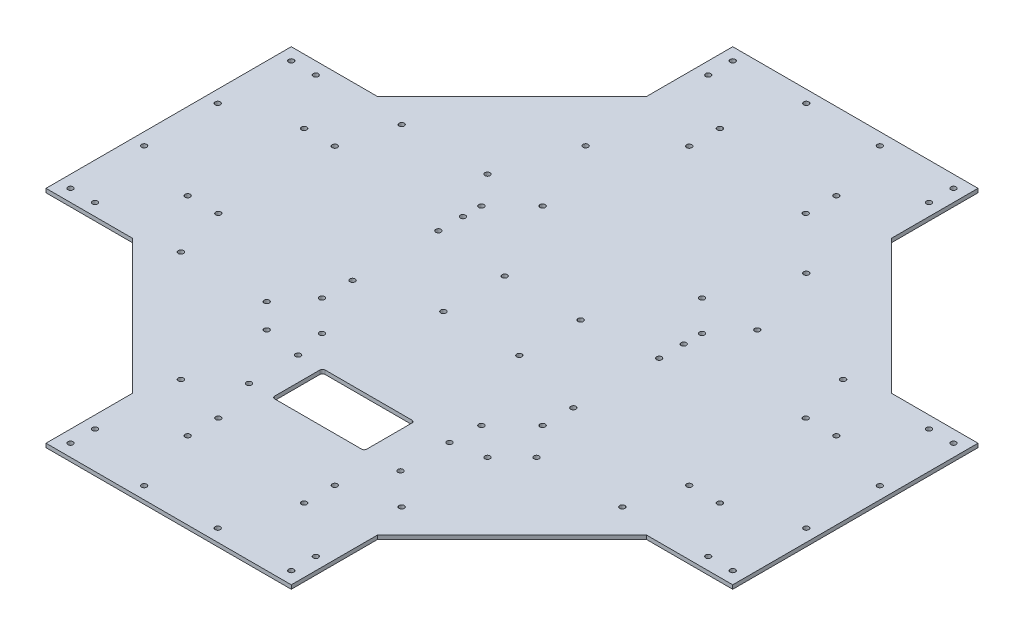
SolidWorks part; units mm, degrees
ref_plane "Front Plane" through (0, 0, 0) normal (0, 0, 1) x (1, 0, 0)
ref_plane "Top Plane" through (0, 0, 0) normal (0, 1, 0) x (1, 0, 0)
ref_plane "Right Plane" through (0, 0, 0) normal (1, 0, 0) x (0, 0, -1)
sketch "Sketch1" plane through (0, 0, 0) normal (0, 1, 0) x (1, 0, 0)
  line L0 (0, -280) -> (100, -280)
  line L1 (100, -280) -> (100, -209.6016)
  line L2 (280, -100) -> (209.6016, -100)
  line L3 (0, 0) -> (0, -280) construction
  line L4 (280, 0) -> (280, -100)
  line L5 (-280, 280) -> (280, 280) construction
  line L6 (-280, 280) -> (-280, -280) construction
  line L7 (-280, -280) -> (280, -280) construction
  line L8 (280, 280) -> (280, -280) construction
  line L9 (-280, 280) -> (280, -280) construction
  line L10 (-280, -280) -> (280, 280) construction
  line L11 (100, -209.6016) -> (209.6016, -100)
  line L12 (-280, 0) -> (-280, -100)
  line L13 (-280, -100) -> (-209.6016, -100)
  line L14 (-209.6016, -100) -> (-100, -209.6016)
  line L15 (-100, -280) -> (-100, -209.6016)
  line L16 (0, -280) -> (-100, -280)
  line L17 (0, 280) -> (-100, 280)
  line L18 (-100, 280) -> (-100, 209.6016)
  line L19 (-100, 209.6016) -> (-209.6016, 100)
  line L20 (-280, 100) -> (-209.6016, 100)
  line L21 (-280, 0) -> (-280, 100)
  line L22 (280, 0) -> (280, 100)
  line L23 (280, 100) -> (209.6016, 100)
  line L24 (209.6016, 100) -> (100, 209.6016)
  line L25 (100, 280) -> (100, 209.6016)
  line L26 (0, 280) -> (100, 280)
  line L27 (111.5258, -219.2889) -> (219.2889, -111.5258) construction
  line L28 (219.2889, -111.5258) -> (247.5732, -139.8101) construction
  line L29 (247.5732, -139.8101) -> (139.8101, -247.5732) construction
  line L30 (139.8101, -247.5732) -> (111.5258, -219.2889) construction
  line L31 (-100, -270) -> (100, -270) construction
  line L32 (-90, -280) -> (-90, 280) construction
  line L33 (-75, -75) -> (75, -75) construction
  line L34 (-75, -75) -> (-75, 75) construction
  line L35 (-75, 75) -> (75, 75) construction
  line L36 (75, -75) -> (75, 75) construction
  line L37 (-75, -75) -> (75, 75) construction
  line L38 (-75, 75) -> (75, -75) construction
  line L39 (-100, -260) -> (100, -260) construction
  line L40 (-280, 40) -> (280, 40) construction
  line L41 (0, 280) -> (0, 0) construction
  line L42 (-280, -90) -> (280, -90) construction
  line L43 (-260, -100) -> (-260, 100) construction
  line L44 (0, 0) -> (-280, 0) construction
  arc A0 (100, -280) -> (280, -100) centre (100, -100) ccw construction
  circle A1 centre (-47.5, -192) radius 2.125
  circle A2 centre (-47.5, -217) radius 2.125
  circle A3 centre (47.5, -217) radius 2.125
  circle A4 centre (47.5, -192) radius 2.125
  circle A5 centre (-192, 47.5) radius 2.125
  circle A6 centre (-217, 47.5) radius 2.125
  circle A7 centre (-192, -47.5) radius 2.125
  circle A8 centre (-217, -47.5) radius 2.125
  circle A9 centre (47.5, 192) radius 2.125
  circle A10 centre (47.5, 217) radius 2.125
  circle A11 centre (-47.5, 192) radius 2.125
  circle A12 centre (-47.5, 217) radius 2.125
  circle A13 centre (192, -47.5) radius 2.125
  circle A14 centre (217, -47.5) radius 2.125
  circle A15 centre (192, 47.5) radius 2.125
  circle A16 centre (217, 47.5) radius 2.125
  circle A17 centre (-90, -270) radius 2.125
  circle A18 centre (-30, -270) radius 2.125
  circle A19 centre (30, -270) radius 2.125
  circle A20 centre (90, -270) radius 2.125
  circle A21 centre (-270, 90) radius 2.125
  circle A22 centre (-270, 30) radius 2.125
  circle A23 centre (-270, -30) radius 2.125
  circle A24 centre (-270, -90) radius 2.125
  circle A25 centre (90, 270) radius 2.125
  circle A26 centre (30, 270) radius 2.125
  circle A27 centre (-30, 270) radius 2.125
  circle A28 centre (-90, 270) radius 2.125
  circle A29 centre (270, -90) radius 2.125
  circle A30 centre (270, -30) radius 2.125
  circle A31 centre (270, 30) radius 2.125
  circle A32 centre (270, 90) radius 2.125
  circle A33 centre (-90, -250) radius 2.125
  circle A34 centre (-90, -180) radius 2.125
  circle A35 centre (-90, -110) radius 2.125
  circle A36 centre (-90, -40) radius 2.125
  circle A37 centre (-90, 30) radius 2.125
  circle A38 centre (-90, 50) radius 2.125
  circle A39 centre (-90, 100) radius 2.125 construction
  circle A40 centre (-90, 150) radius 2.125
  circle A41 centre (-90, 200) radius 2.125 construction
  circle A42 centre (-90, 250) radius 2.125
  circle A43 centre (90, -250) radius 2.125
  circle A44 centre (90, -180) radius 2.125
  circle A45 centre (90, -110) radius 2.125
  circle A46 centre (90, -40) radius 2.125
  circle A47 centre (90, 30) radius 2.125
  circle A48 centre (90, 50) radius 2.125
  circle A49 centre (90, 100) radius 2.125 construction
  circle A50 centre (90, 150) radius 2.125
  circle A51 centre (90, 200) radius 2.125 construction
  circle A52 centre (90, 250) radius 2.125
  circle A53 centre (-250, -90) radius 2.125
  circle A54 centre (-180, -90) radius 2.125
  circle A55 centre (-110, -90) radius 2.125
  circle A56 centre (-110, 90) radius 2.125
  circle A57 centre (-180, 90) radius 2.125
  circle A58 centre (-250, 90) radius 2.125
  circle A59 centre (110, -90) radius 2.125
  circle A60 centre (180, -90) radius 2.125
  circle A61 centre (250, -90) radius 2.125
  circle A62 centre (110, 90) radius 2.125
  circle A63 centre (180, 90) radius 2.125
  circle A64 centre (250, 90) radius 2.125
  point P33 (0, 0)
  point P68 (0, 0)
  point P107 (0, 0)
  dimension "D10" = 25
  dimension "4.25" = 4.25
  dimension "D11" = 4.25
  dimension "D16" = 4.25
  dimension "D24" = 4.25
  dimension "D28" = 4.25
  dimension "D32" = 4.25
  dimension "D1" = 560
  dimension "D2" = 90
  dimension "D3" = 280
  dimension "D4" = 4
  dimension "D5" = 100
  dimension "D6" = 155
  dimension "D7" = 152.4
  dimension "D8" = 15
  dimension "D9" = 40
  dimension "D12" = 47.5
  dimension "D13" = 63
  dimension "D15" = 10
  dimension "D17" = 10
  dimension "D18" = 76.2
  dimension "D19" = 150
  dimension "D20" = 150
  dimension "D23" = 10
  dimension "D25" = 10
  dimension "D26" = 300
  dimension "D29" = 10
  dimension "D31" = 20
  dimension "D33" = 10
  dimension "D21" = 4
  dimension "D27" = 5
  dimension "D30" = 5
  dimension "D34" = 3
  dimension "D14" = 4
  dimension "D22" = 4
extrude "Boss-Extrude1" add sketch "Sketch1" along normal blind 3.175 contours L26 L17 L18 L19 L20 L21 L12 L13 L14 L15 L16 L0 L1 L11 L2 L4 L22 L23 L24 L25 region at (0, 0, -0.0137)
sketch "Sketch2" plane through (0, 3.175, 0) normal (0, 1, 0) x (1, 0, 0)
  line L0 (0, 25.5202) -> (0, -25) construction
  line L1 (-31, -25) -> (31, -25) construction
  line L2 (-31, -25) -> (-31, 25) construction
  line L3 (-31, 25) -> (31, 25) construction
  line L4 (31, -25) -> (31, 25) construction
  line L5 (-31, -25) -> (31, 25) construction
  line L6 (-31, 25) -> (31, -25) construction
  line L7 (75, -75) -> (75, 75) construction
  line L8 (-75, -75) -> (75, -75) construction
  line L9 (-75, -75) -> (-75, 75) construction
  line L10 (-75, 75) -> (75, 75) construction
  line L11 (75, -75) -> (75, 75) construction
  line L12 (-75, -75) -> (75, -75) construction
  line L13 (-75, -75) -> (-75, 75) construction
  line L14 (-75, 75) -> (75, 75) construction
  line L15 (-90, 270) -> (-90, -270) construction
  line L16 (-270, 90) -> (270, 90) construction
  line L17 (-40.0349, -135) -> (34.9651, -135) construction
  line L18 (-40.0349, -155.5) -> (34.9651, -155.5)
  line L19 (-40.0349, -155.5) -> (-40.0349, -114.5)
  line L20 (-40.0349, -114.5) -> (34.9651, -114.5)
  line L21 (34.9651, -155.5) -> (34.9651, -114.5)
  line L22 (-40.0349, -155.5) -> (34.9651, -114.5) construction
  line L23 (-40.0349, -114.5) -> (34.9651, -155.5) construction
  circle A0 centre (-31, 25) radius 2.125
  circle A1 centre (-31, -25) radius 2.125
  circle A2 centre (31, -25) radius 2.125
  circle A3 centre (31, 25) radius 2.125
  circle A4 centre (-90, 65) radius 2.125
  circle A5 centre (-65, 90) radius 2.125
  circle A6 centre (65, 90) radius 2.125
  circle A7 centre (90, 65) radius 2.125
  circle A8 centre (90, -65) radius 2.125
  circle A9 centre (65, -90) radius 2.125
  circle A10 centre (-65, -90) radius 2.125
  circle A11 centre (-90, -65) radius 2.125
  circle A12 centre (64.0651, -115) radius 2.125
  circle A13 centre (64.0651, -155) radius 2.125
  circle A14 centre (-59.4349, -115) radius 2.125
  circle A15 centre (-59.4349, -155) radius 2.125
  point P0 (0, 0)
  point P28 (-2.5349, -135)
  point P43 (0, 0)
  dimension "D3" = 4.25
  dimension "D4" = 4.25
  dimension "D5" = 4.25
  dimension "D7" = 4.25
  dimension "D13" = 4.25
  dimension "D16" = 4.25
  dimension "D1" = 62
  dimension "D2" = 50
  dimension "D6" = 10
  dimension "D8" = 10
  dimension "D10" = 41
  dimension "D11" = 75
  dimension "D12" = 135
  dimension "D14" = 20
  dimension "D15" = 66.6
  dimension "D17" = 19.4
  dimension "D18" = 20
  dimension "D9" = 4
extrude "Cut-Extrude1" cut sketch "Sketch2" against normal through all
fillet "Fillet1" radius 2 4 edges at (34.9651, 1.5875, 114.5) (34.9651, 1.5875, 155.5) (-40.0349, 1.5875, 155.5) (-40.0349, 1.5875, 114.5)
